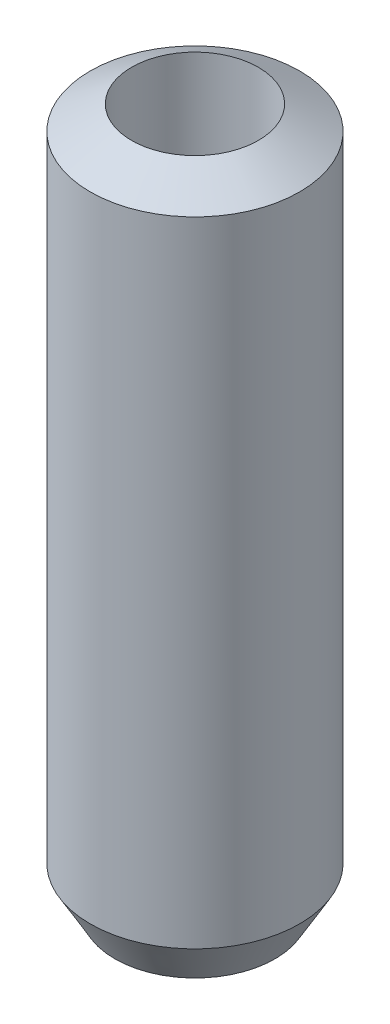
SolidWorks part; units mm, degrees
ref_plane "Front Plane" through (0, 0, 0) normal (0, 0, 1) x (1, 0, 0)
ref_plane "Top Plane" through (0, 0, 0) normal (0, 1, 0) x (1, 0, 0)
ref_plane "Right Plane" through (0, 0, 0) normal (1, 0, 0) x (0, 0, -1)
sketch "Sketch1" plane through (0, 0, 0) normal (0, 1, 0) x (1, 0, 0)
  circle A0 centre (0, 0) radius 25
  dimension "SHAFT_OD" = 50
extrude "Boss-Extrude1" add sketch "Sketch1" along normal blind 167.3509
sketch "Sketch2" plane through (0, 0, 0) normal (0, 1, 0) x (1, 0, 0)
  circle A0 centre (0, 0) radius 15.1366
  dimension "BORE_D" = 30.2733
extrude "Cut-Extrude1" cut sketch "Sketch2" along normal through all
chamfer "Chamfer1" distance 5.8782 angle 60 2 edges at (0, 167.3509, 25) (0, 0, 25) first distance on face at (0, 167.3509, 25) first distance on face at (0, 0, 15.1366)
